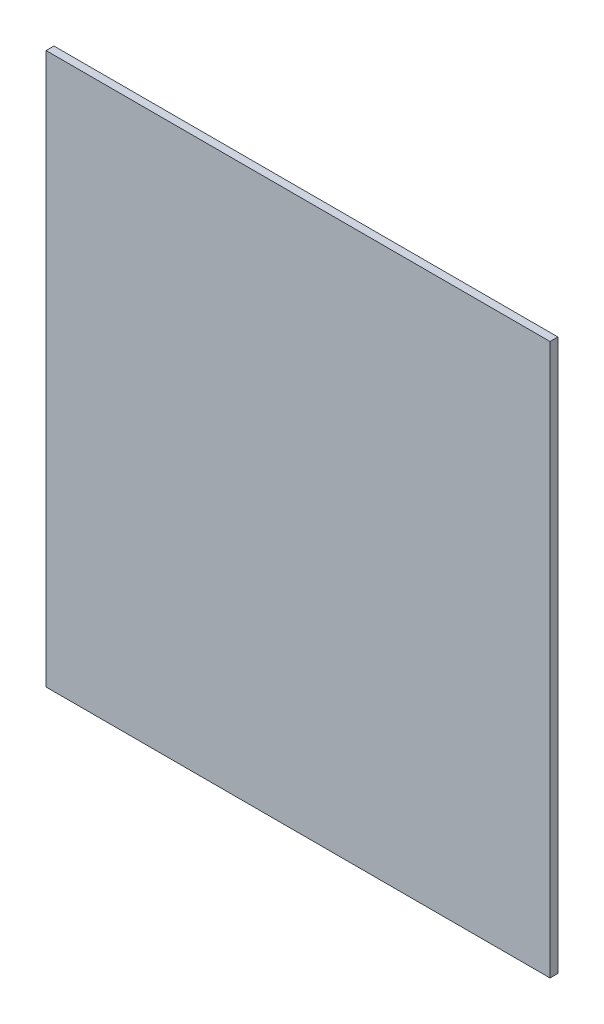
SolidWorks part; units mm, degrees
material "Oak"
ref_plane "Front Plane" through (0, 0, 0) normal (0, 0, 1) x (1, 0, 0)
ref_plane "Top Plane" through (0, 0, 0) normal (0, 1, 0) x (1, 0, 0)
ref_plane "Right Plane" through (0, 0, 0) normal (1, 0, 0) x (0, 0, -1)
sketch "Sketch1" plane through (0, 0, 0) normal (0, 0, 1) x (1, 0, 0)
  line L1 (-160, 175) -> (160, 175)
  line L2 (-160, 175) -> (-160, -175)
  line L3 (-160, -175) -> (160, -175)
  line L4 (160, 175) -> (160, -175)
  line L5 (-160, 175) -> (160, -175) construction
  line L6 (-160, -175) -> (160, 175) construction
  point P0 (0, 0)
  dimension "D1" = 320
  dimension "D2" = 350
base flange "Base-Flange1" sketch "Sketch1" thickness 5 reverse thickness direction no parameters "D1"=0.7366
sketch "Bend-Lines1" [suppressed] plane through (0, 0, 0) normal (0, 1, 0) x (1, 0, 0)
sketch "Bounding-Box1" [suppressed] plane through (0, 0, 0) normal (0, 1, 0) x (1, 0, 0)
sheet metal parameters "Sheet-Metal1" thickness 5 parameters "D1"=0.7366
flat pattern "Flat-Pattern1" [suppressed]
sketch "Bend-Lines2" plane through (0, 0, 0) normal (0, 1, 0) x (1, 0, 0)
sketch3d "Bounding-Box2" [suppressed]
  line L0 (-160, 175, 0) -> (-160, -175, 0) construction
  line L1 (160, 175, 0) -> (160, -175, 0) construction
  line L2 (-160, 175, 0) -> (160, 175, 0) construction
  line L3 (-160, -175, 0) -> (160, -175, 0) construction
